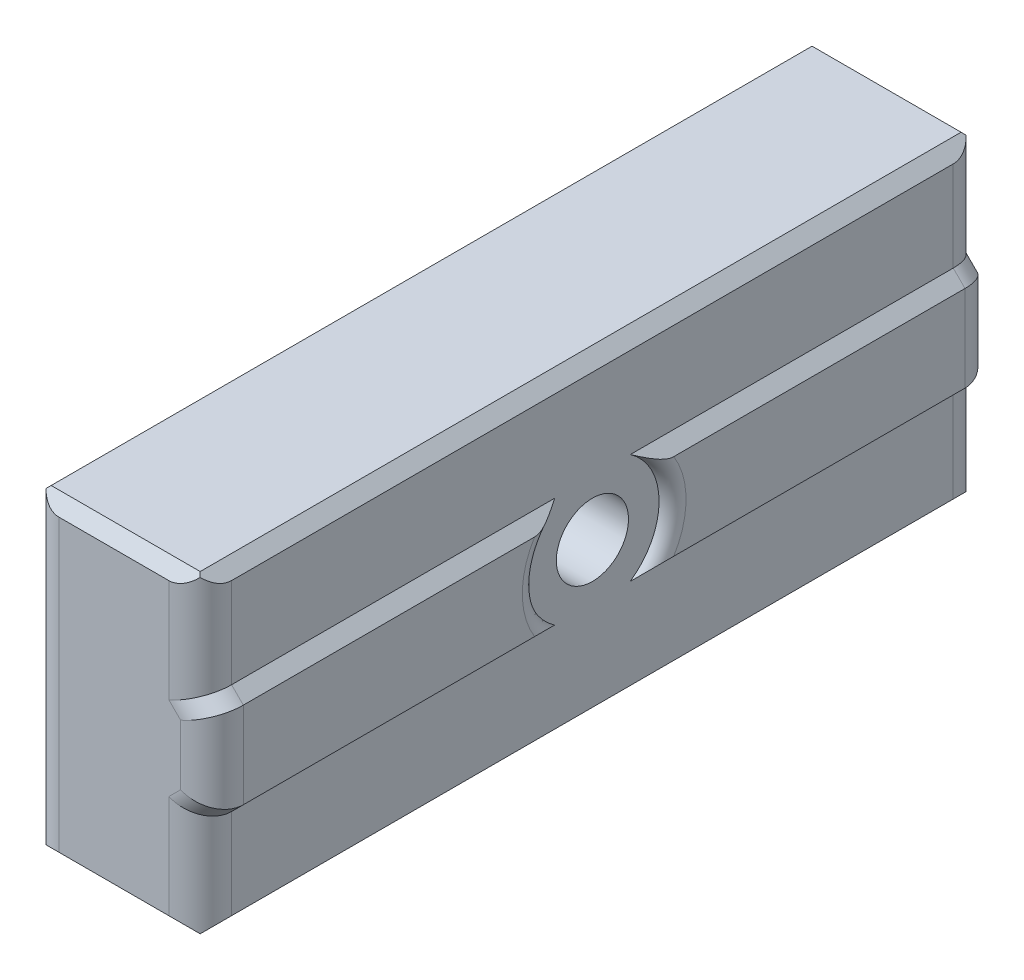
SolidWorks part; units mm, degrees
ref_plane "Front" through (0, 0, 0) normal (0, 0, 1) x (1, 0, 0)
ref_plane "Top" through (0, 0, 0) normal (0, 1, 0) x (1, 0, 0)
ref_plane "Right" through (0, 0, 0) normal (1, 0, 0) x (0, 0, -1)
sketch "Skizze3" plane through (0, 0, 0) normal (0, 0, 1) x (1, 0, 0)
  line L0 (11, 0) -> (11, -23.2454) construction
  line L1 (100, 0) -> (0, 0) construction
  line L2 (0, -0.6771) -> (0, -119.3229) construction
  line L3 (0, 0) -> (11, 0)
  line L4 (11, 0) -> (11, -20)
  line L5 (0, 0) -> (0, -20)
  line L6 (0, -20) -> (11, -20)
  dimension "D1" = 11
  dimension "D2" = 20
extrude "Aufsatz-Linear austragen1" add sketch "Skizze3" against normal blind 50
sketch "Skizze4" plane through (0, 0, 0) normal (-1, 0, 0) x (0, 0, 1)
  circle A0 centre (-40, -7) radius 2.375
  circle A1 centre (-10, -7) radius 2.375
  dimension "D1" = 4.75
  dimension "D2" = 4.75
extrude "Schnitt-Linear austragen1" cut sketch "Skizze4" against normal blind 10
sketch "Skizze7" plane through (0, 0, 0) normal (0, 0, 1) x (1, 0, 0)
  line L0 (11, -10) -> (19.0417, -10) construction
  line L1 (11, -20) -> (11, 0) construction
  line L2 (11, -13.5) -> (11, -6.5)
  line L3 (11, -6.5) -> (11.75, -7.25)
  line L4 (11.75, -7.25) -> (11.75, -12.75)
  line L5 (11, -13.5) -> (11.75, -12.75)
  point P4 (11.75, -7.0945)
  point P9 (11.75, -10)
  dimension "D1" = 0.75
  dimension "D2" = 7
  dimension "D3" = 45
extrude "Aufsatz-Linear austragen2" add sketch "Skizze7" against normal up to surface (50 mm away) up to face at (5.5, -10, -50)
sketch "Skizze5" plane through (0, 0, 0) normal (-1, 0, 0) x (0, 0, 1)
  line L0 (-50, -10) -> (0, -10) construction
  line L1 (-50, 0) -> (-50, -20) construction
  line L2 (0, 0) -> (0, -20) construction
  circle A0 centre (-25, -10) radius 2.3
  dimension "D1" = 4.6
extrude "Schnitt-Linear austragen2" cut sketch "Skizze5" against normal through all
sketch "Skizze6" plane through (0, 0, 0) normal (-1, 0, 0) x (0, 0, 1)
  circle A0 centre (-25, -10) radius 3.75
  dimension "D1" = 7.5
extrude "Schnitt-Linear austragen3" cut sketch "Skizze6" against normal offset from surface (4.5 mm away) 6.5 up to face at (11, -16.75, -25)
sketch "Skizze8" plane through (11, 0, 0) normal (1, 0, 0) x (0, 0, -1)
  circle A0 centre (25, -10) radius 4.25
  dimension "D1" = 8.5
extrude "Schnitt-Linear austragen4" cut sketch "Skizze8" along normal blind 6.5
fillet "Verrundung1" radius 1 2 edges at (11.75, -10, -20.75) (11.75, -10, -29.25)
chamfer "Fase1" distance 0.75 angle 45 8 edges at (0, 0, -25) (5.5, 0, -50) (11, 0, -25) (5.5, 0, 0) (11, -20, -25) (5.5, -20, -50) (0, -20, -25) (5.5, -20, 0)
fillet "Verrundung2" radius 2 12 edges at (11, -16.375, 0) (11.375, -13.125, 0) (11.75, -10, 0) (11.375, -6.875, 0) (11, -3.625, 0) (11, -16.375, -50) (11.375, -13.125, -50) (11.75, -10, -50) (11.375, -6.875, -50) (11, -3.625, -50) (0, -10, 0) (0, -10, -50)
